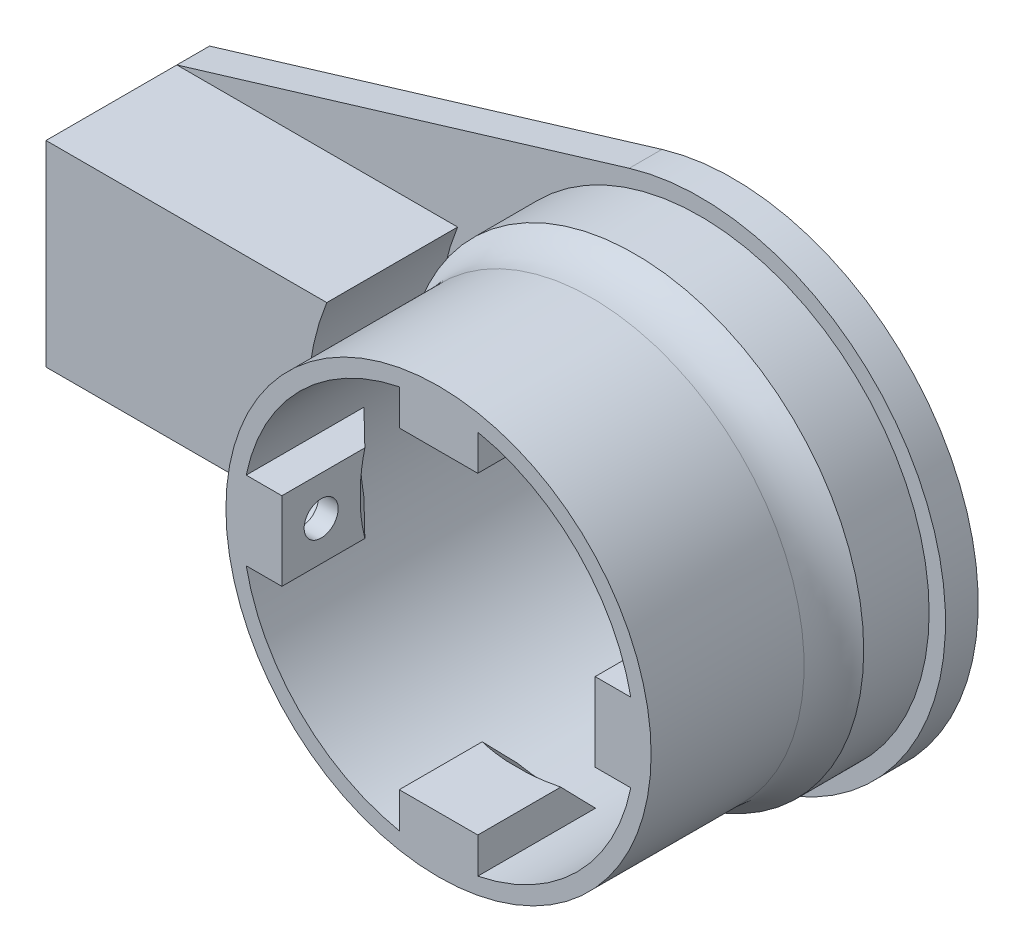
SolidWorks part; units mm, degrees
ref_plane "Plan de face" through (0, 0, 0) normal (0, 0, 1) x (1, 0, 0)
ref_plane "Plan de dessus" through (0, 0, 0) normal (0, 1, 0) x (1, 0, 0)
ref_plane "Plan de droite" through (0, 0, 0) normal (1, 0, 0) x (0, 0, -1)
sketch "Esquisse1" plane through (0, 0, 0) normal (0, 0, 1) x (1, 0, 0)
  line L0 (-1000, 0) -> (49000, 0) construction
  line L1 (-10.8475, 35.8968) -> (-80, 15)
  line L2 (-80, 15) -> (-80, -15)
  line L3 (-10.8475, -35.8968) -> (-80, -15)
  arc A0 (-10.8475, -35.8968) -> (-10.8475, 35.8968) centre (0, 0) ccw
  circle A1 centre (0, 0) radius 30
  point P9 (-80, 0)
  dimension "D1" = 75
  dimension "D4" = 60
  dimension "D2" = 15
  dimension "D3" = 80
extrude "Boss.-Extru.1" add sketch "Esquisse1" along normal blind 5
sketch "Esquisse6" plane through (0, 0, 5) normal (0, 0, 1) x (1, 0, 0)
  circle A0 centre (0, 0) radius 35
  circle A1 centre (0, 0) radius 30
  dimension "D1" = 70
  dimension "D2" = 60
extrude "Boss.-Extru.6" add sketch "Esquisse6" along normal blind 10
sketch "Esquisse7" plane through (0, 0, 15) normal (0, 0, 1) x (1, 0, 0)
  circle A0 centre (0, 0) radius 30
  circle A1 centre (0, 0) radius 32.5
  dimension "D1" = 65
extrude "Boss.-Extru.8" add sketch "Esquisse7" along normal blind 30
fillet "Congé2" radius 10 1 edges at (32.5, 0, 15)
sketch "Esquisse8" plane through (0, 0, 5) normal (0, 0, 1) x (1, 0, 0)
  line L0 (-80, 15) -> (-37.081, 15)
  line L1 (-1000, 0) -> (49000, 0) construction
  line L2 (-80, 15) -> (-80, -15)
  line L3 (-80, 15) -> (-80, -15) construction
  line L4 (-80, -15) -> (-37.081, -15)
  arc A0 (-37.081, 15) -> (-37.081, -15) centre (0, 0) ccw
  point P12 (-80, 0)
  dimension "D1" = 80
extrude "Boss.-Extru.9" add sketch "Esquisse8" along normal blind 20
sketch "Esquisse9" plane through (0, 0, 45) normal (0, 0, 1) x (1, 0, 0)
  line L1 (-23.9414, -6) -> (-31.9414, -6)
  line L2 (-23.9414, -6) -> (-23.9414, 6)
  line L3 (-23.9414, 6) -> (-31.9414, 6)
  line L4 (-31.9414, -6) -> (-31.9414, 6)
  line L5 (-23.9414, -6) -> (-31.9414, 6) construction
  line L6 (-23.9414, 6) -> (-31.9414, -6) construction
  line L18 (-6, 23.9414) -> (6, 23.9414)
  line L19 (-6, 23.9414) -> (-6, 31.9414)
  line L20 (-6, 31.9414) -> (6, 31.9414)
  line L21 (6, 23.9414) -> (6, 31.9414)
  line L22 (23.9414, 6) -> (23.9414, -6)
  line L23 (23.9414, 6) -> (31.9414, 6)
  line L24 (31.9414, 6) -> (31.9414, -6)
  line L25 (23.9414, -6) -> (31.9414, -6)
  line L26 (6, -23.9414) -> (-6, -23.9414)
  line L27 (6, -23.9414) -> (6, -31.9414)
  line L28 (6, -31.9414) -> (-6, -31.9414)
  line L29 (-6, -23.9414) -> (-6, -31.9414)
  circle A0 centre (0, 0) radius 32.5 construction
  point P0 (-27.9414, 0)
  point P22 (0, 0)
  dimension "D1" = 8
  dimension "D3" = 12
  dimension "D2" = 4
extrude "Boss.-Extru.10" add sketch "Esquisse9" against normal blind 12
chamfer "Chanfrein1" distance 6 angle 45 4 edges at (0, 30, 33) (30, 0, 33) (0, -30, 33) (-30, 0, 33)
sketch "Esquisse10" plane through (-23.9414, 0, 0) normal (1, 0, 0) x (0, 0, -1)
  line L0 (-45, 32.5) -> (-45, -32.5) construction
  circle A0 centre (-39, 0) radius 4.5
  dimension "D1" = 9
  dimension "D2" = 6
extrude "Enlèv. mat.-Extru.1" cut sketch "Esquisse10" against normal up to next
sketch "Esquisse12" plane through (-23.9414, 0, 0) normal (1, 0, 0) x (0, 0, -1)
  line L0 (-45, 32.5) -> (-45, -32.5) construction
  circle A0 centre (-39, 0) radius 4.5
  circle A1 centre (-39, 0) radius 2.6
  dimension "D1" = 6
  dimension "9" = 9
  dimension "D2" = 5.2
extrude "Boss.-Extru.11" add sketch "Esquisse12" against normal blind 3
